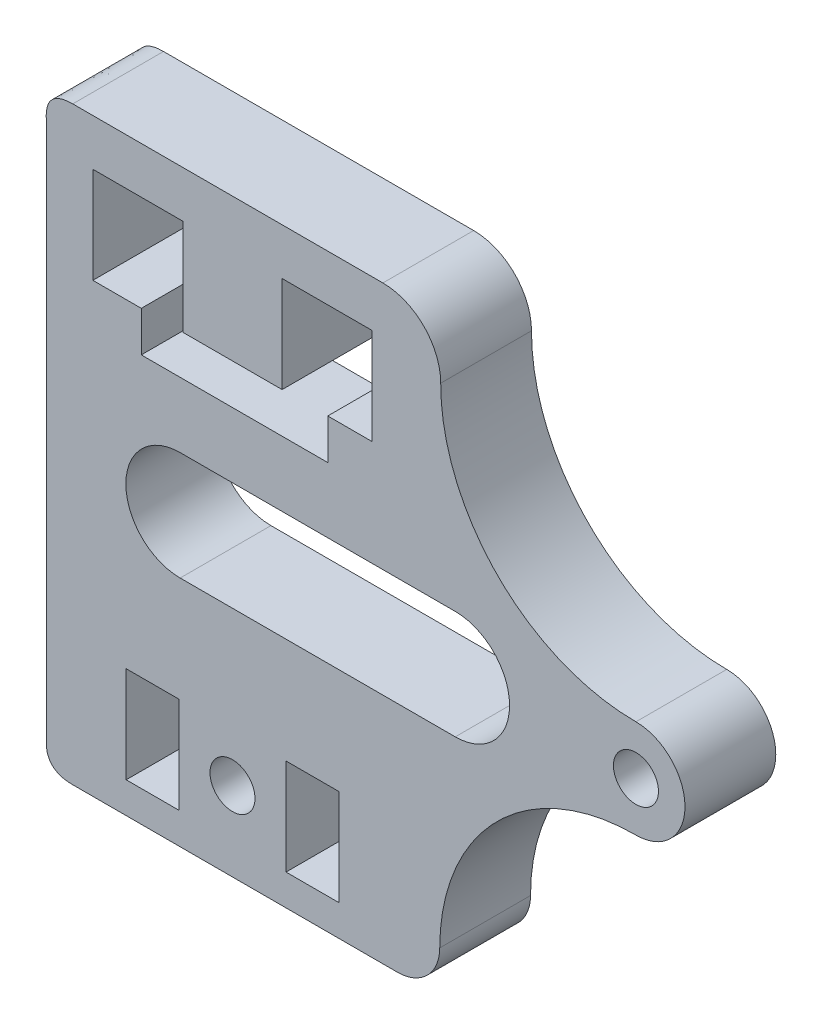
SolidWorks part; units mm, degrees
material "Acrylic (Medium-high impact)"
ref_plane "Front Plane" through (0, 0, 0) normal (0, 0, 1) x (1, 0, 0)
ref_plane "Top Plane" through (0, 0, 0) normal (0, 1, 0) x (1, 0, 0)
ref_plane "Right Plane" through (0, 0, 0) normal (1, 0, 0) x (0, 0, -1)
sketch "Sketch1" plane through (0, 0, 0) normal (0, 0, 1) x (1, 0, 0)
  line L0 (405.6988, 552.3389) -> (405.6988, 554.9389)
  line L1 (396.361, 554.9389) -> (402.7571, 554.9389)
  line L2 (393.683, 554.9389) -> (393.683, 552.3389)
  line L3 (393.683, 552.3389) -> (405.6988, 552.3389)
  line L4 (390.561, 561.1389) -> (390.561, 554.9389)
  line L5 (393.683, 554.9389) -> (390.561, 554.9389)
  line L6 (396.361, 561.1389) -> (390.561, 561.1389)
  line L7 (396.361, 554.9389) -> (396.361, 561.1389)
  line L8 (405.6988, 554.9389) -> (408.5571, 554.9389)
  line L9 (408.5571, 554.9389) -> (408.5571, 561.1389)
  line L10 (402.7571, 561.1389) -> (402.7571, 554.9389)
  line L11 (408.5571, 561.1389) -> (402.7571, 561.1389)
  line L12 (392.709, 534.3389) -> (392.709, 528.1389)
  line L13 (392.709, 528.1389) -> (396.109, 528.1389)
  line L14 (396.109, 534.3389) -> (392.709, 534.3389)
  line L15 (396.109, 528.1389) -> (396.109, 534.3389)
  line L16 (403.009, 528.1389) -> (406.4091, 528.1389)
  line L17 (406.4091, 528.1389) -> (406.4091, 534.3389)
  line L18 (403.009, 534.3389) -> (403.009, 528.1389)
  line L19 (406.4091, 534.3389) -> (403.009, 534.3389)
  line L20 (389.2659, 564.1389) -> (409.2527, 564.1389)
  line L21 (387.561, 562.4358) -> (387.561, 527.842)
  line L22 (389.2659, 526.1389) -> (410.1905, 526.1389)
  line L23 (-606.039, 561.1389) -> (49393.961, 561.1389) construction
  line L24 (396.1883, 548.1389) -> (413.9157, 548.1389)
  line L25 (396.1883, 541.1389) -> (413.9157, 541.1389)
  line L26 (-600.441, 544.6389) -> (49399.559, 544.6389) construction
  line L27 (398.109, 531.2389) -> (396.109, 531.2389) construction
  line L28 (401.009, 531.2389) -> (403.009, 531.2389) construction
  line L29 (399.559, -466.6171) -> (399.559, 49533.3829) construction
  line L30 (425.559, -455.7473) -> (425.559, 49544.2527) construction
  line L31 (-599.1986, 528.1389) -> (49400.8014, 528.1389) construction
  line L32 (421.9074, 544.6389) -> (421.9074, 528.1389) construction
  line L33 (421.9074, 544.6389) -> (421.9074, 561.1389) construction
  line L34 (412.9774, 560.4069) -> (412.9155, 528.8585) construction
  circle A0 centre (425.559, 544.6389) radius 1.45
  arc A1 (396.1883, 548.1389) -> (396.1883, 541.1389) centre (396.1883, 544.6389) ccw
  circle A2 centre (399.559, 531.2389) radius 1.45
  arc A3 (412.9155, 528.8585) -> (425.559, 541.4773) centre (425.559, 528.8337) cw
  arc A4 (412.9774, 560.4069) -> (425.559, 547.8005) centre (425.559, 560.3822) ccw
  arc A5 (425.559, 547.8005) -> (425.559, 541.4773) centre (425.559, 544.6389) cw
  arc A7 (413.9157, 548.1389) -> (413.9157, 541.1389) centre (413.9157, 544.6389) cw
  arc A8 (410.1905, 526.1389) -> (412.9155, 528.8585) centre (410.1905, 528.8639) ccw
  arc A9 (409.2527, 564.1389) -> (412.9774, 560.4069) centre (409.2527, 560.4142) cw
  spline S36 degree 2 poles (387.561, 562.4358) (387.4672, 564.1389) (389.2659, 564.1389) knots 0 0 0 1 1 1
  spline S37 degree 2 poles (387.561, 527.842) (387.4672, 526.1389) (389.2659, 526.1389) knots 0 0 0 1 1 1
  point P26 (399.559, 544.6389)
  point P30 (399.559, 554.9389)
  dimension "D5" = 2.9
  dimension "D1" = 6.2
  dimension "D2" = 3.4
  dimension "D3" = 5.8
  dimension "D4" = 2.6
  dimension "D6" = 2
  dimension "D7" = 33
  dimension "D8" = 2
  dimension "D9" = 3
  dimension "D10" = 3
  dimension "D11" = 26
extrude "Boss-Extrude2" add sketch "Sketch1" along normal blind 5.85
